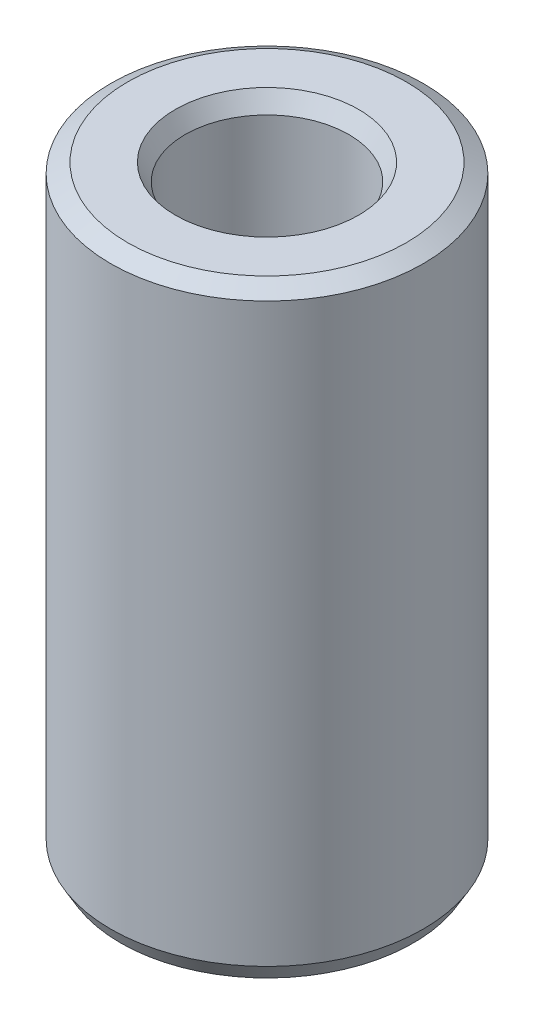
SolidWorks part; units mm, degrees
ref_plane "Front Plane" through (0, 0, 0) normal (0, 0, 1) x (1, 0, 0)
ref_plane "Top Plane" through (0, 0, 0) normal (0, 1, 0) x (1, 0, 0)
ref_plane "Right Plane" through (0, 0, 0) normal (1, 0, 0) x (0, 0, -1)
sketch "Sketch1" plane through (0, 0, 0) normal (0, 1, 0) x (1, 0, 0)
  circle A0 centre (0, 0) radius 60
  dimension "SLEEVE_OD" = 120
extrude "Boss-Extrude1" add sketch "Sketch1" along normal blind 231.5719
sketch "Sketch2" plane through (0, 0, 0) normal (0, 1, 0) x (1, 0, 0)
  circle A0 centre (0, 0) radius 31.4629
  dimension "BORE_D" = 62.9258
extrude "Cut-Extrude1" cut sketch "Sketch2" along normal through all
chamfer "Chamfer1" distance 3.7442 angle 60 4 edges at (0, 231.5719, 31.4629) (0, 0, 31.4629) (0, 0, 60) (0, 231.5719, 60) first distance on face at (0, 231.5719, 31.4629) first distance on face at (0, 0, 31.4629) first distance on face at (0, 231.5719, 60)
